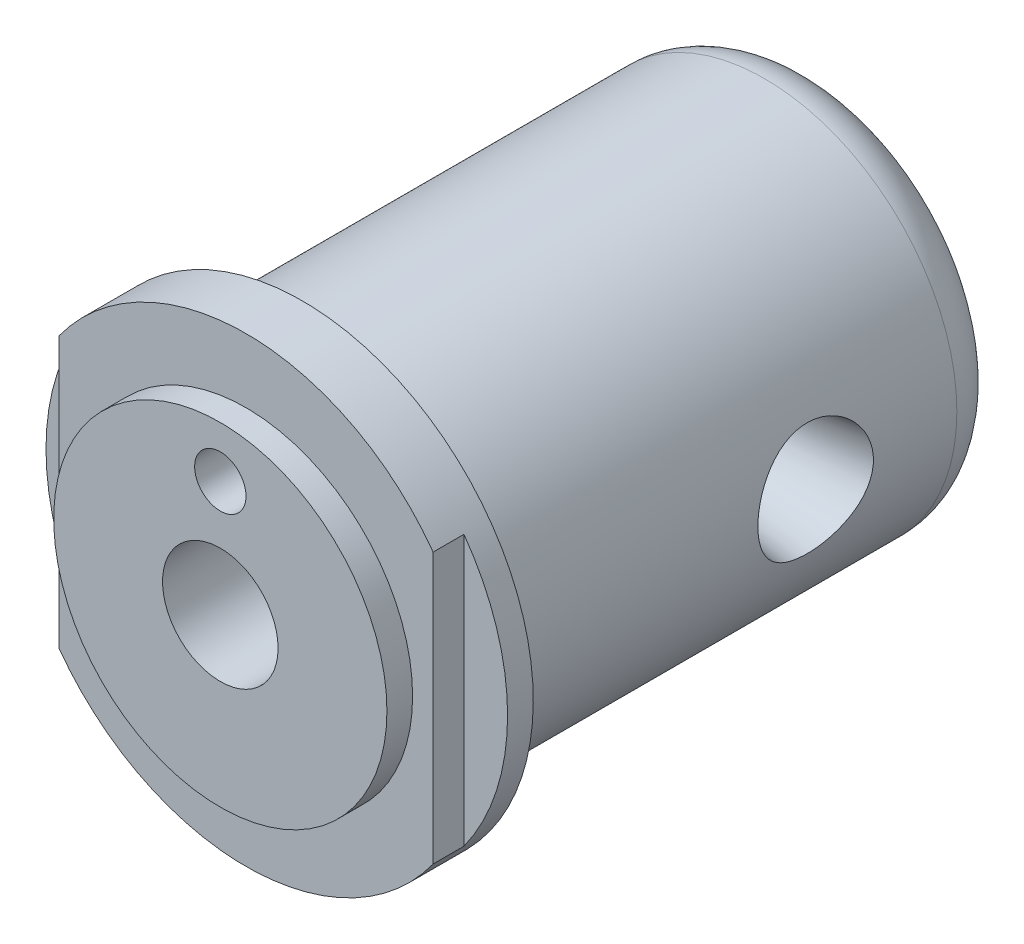
SolidWorks part; units mm, degrees
note: The reader was unsure of these and kept them because the rebuilt part matched: shared geometry of "Sketch1<3>".
material "6061 Alloy"
ref_plane "Front Plane" through (0, 0, 0) normal (0, 0, 1) x (1, 0, 0)
ref_plane "Top Plane" through (0, 0, 0) normal (0, 1, 0) x (1, 0, 0)
ref_plane "Right Plane" through (0, 0, 0) normal (1, 0, 0) x (0, 0, -1)
sketch "Sketch1" plane through (0, 0, 0) normal (0, 0, 1) x (1, 0, 0)
  line L1 (-7.29, -8.99) -> (7.29, -8.99)
  line L2 (-7.29, -8.99) -> (-7.29, 8.99)
  line L3 (-7.29, 8.99) -> (7.29, 8.99)
  line L4 (7.29, -8.99) -> (7.29, 8.99)
  line L5 (-7.29, -8.99) -> (7.29, 8.99) construction
  line L6 (-7.29, 8.99) -> (7.29, -8.99) construction
  circle A0 centre (0, 0) radius 6.49
  circle A1 centre (0, 0) radius 2 construction
  circle A2 centre (0, 4.5) radius 1
  circle A3 centre (0, 0) radius 8.99
  dimension "D1" = 12.98
  dimension "D3" = 2
  dimension "D4" = 4
  dimension "D5" = 17.98
  dimension "D2" = 4.5
  dimension "D6" = 14.58
extrude "Boss-Extrude1" add sketch "Sketch1" along normal blind 1 contours A0 A2 | A2
extrude "Boss-Extrude2" add sketch "Sketch1<3>" against normal blind 1.2 contours L4 A3 L2 A0 | A0 A2 | A2
sketch "Sketch1<3>" plane through (0, 0, 0) normal (0, 0, 1) x (1, 0, 0) same geometry as "Sketch1"
sketch "Sketch2" plane through (0, 0, -1.2) normal (0, 0, -1) x (-1, 0, 0)
  line L4 (-7.29, -8.99) -> (7.29, -8.99)
  line L5 (-7.29, 8.99) -> (-7.29, -8.99)
  line L6 (7.29, 8.99) -> (-7.29, 8.99)
  line L7 (7.29, -8.99) -> (7.29, 8.99)
  line L8 (-7.29, -8.99) -> (7.29, -8.99)
  line L9 (-7.29, 8.99) -> (-7.29, -8.99)
  line L10 (7.29, 8.99) -> (-7.29, 8.99)
  line L11 (7.29, -8.99) -> (7.29, 8.99)
  circle A1 centre (0, 0) radius 8.99
  circle A2 centre (0, 0) radius 8.99
  circle A3 centre (0, 4.5) radius 1
  circle A4 centre (0, 4.5) radius 1
  circle A5 centre (0, 0) radius 6.49
  circle A6 centre (0, 0) radius 6.49
  dimension "D1" = 0
  dimension "D2" = 0
  dimension "D3" = 0
  dimension "D4" = 0
extrude "Boss-Extrude3" add sketch "Sketch2" along normal blind 1
sketch "Sketch3" plane through (0, 0, -2.2) normal (0, 0, -1) x (-1, 0, 0)
  circle A0 centre (0, 0) radius 7.49
  circle A1 centre (0, 0) radius 8.99
  circle A2 centre (0, 0) radius 8.99
  dimension "D2" = 14.98
  dimension "D1" = 0
extrude "Boss-Extrude4" add sketch "Sketch3" along normal blind 20
sketch "Sketch4" plane through (0, 0, -22.2) normal (0, 0, -1) x (-1, 0, 0)
  circle A0 centre (0.1601, 0) radius 5
  circle A1 centre (0, 0) radius 7.49
  circle A2 centre (0, 0) radius 7.49
  dimension "D2" = 14.98
  dimension "D3" = 10
  dimension "D1" = 0
hole_wizard "Ø7.0 (7) Diameter Hole1" positions "Sketch5" profile "Sketch6" hole size "Ø7.0" standard "ISO"
sketch "Sketch5" plane through (0, 0, -22.2) normal (0, 0, -1) x (-1, 0, 0)
  point P0 (0, 0)
sketch "Sketch6" plane through (0, 0, -22.2) normal (1, 0, 0) x (0, 1, 0)
  line L0 (0, 0) -> (0, 16.7)
  line L1 (0, 16.7) -> (3.5, 16.7)
  line L2 (3.5, 16.7) -> (3.5, 0)
  line L5 (3.5, 0) -> (0, 0)
  line L10 (0, 16.7) -> (-3.5, 16.7) construction
  line L11 (0, -6.35) -> (0, 107.95) construction
  dimension "Hole Dia." = 7
  dimension "Hole Depth" = 16.7
  dimension "Drill Angle" = 180
sketch "Sketch7" plane through (0, 0, 1) normal (0, 0, 1) x (1, 0, 0)
  circle A0 centre (0, 4.5) radius 1 construction
  circle A1 centre (0, 4.5) radius 1
  circle A2 centre (0, 0) radius 2 construction
  circle A3 centre (0, 0) radius 2
hole_wizard "Ø2.0mm Dowel Hole1" positions "Sketch8" profile "Sketch9" hole size "Ø2.0" standard "ISO"
sketch "Sketch8" plane through (0, 0, 1) normal (0, 0, 1) x (1, 0, 0)
  point P0 (0, 4.5)
sketch "Sketch9" plane through (0, 4.5, 1) normal (1, 0, 0) x (0, -1, 0)
  line L0 (0, 0) -> (0, 4.6009)
  line L1 (0, 4.6009) -> (1, 4)
  line L2 (1, 4) -> (1, 0)
  line L5 (1, 0) -> (0, 0)
  line L10 (0, 4.6009) -> (-1, 4) construction
  line L11 (0, -6.35) -> (0, 107.95) construction
  dimension "Hole Dia." = 2
  dimension "Hole Depth" = 4
  dimension "Drill Angle" = 118
fillet "Fillet1" radius 2 1 edges at (-7.49, 0, -22.2)
ref_plane "Plane1" through (7.49, 0, 0) normal (1, 0, 0) x (0, 0, -1)
sketch "Sketch10" plane through (7.49, 0, 0) normal (1, 0, 0) x (0, 0, -1)
  line L0 (-1, -6.49) -> (-1, 6.49)
  line L1 (-1, -6.49) -> (-1, 6.49) construction
  line L2 (-1, 6.49) -> (0, 6.49)
  line L3 (-1, 6.49) -> (0, 6.49) construction
  line L4 (0, 6.49) -> (0, 8.99)
  line L5 (0, 6.49) -> (0, 8.99) construction
  line L6 (0, 8.99) -> (2.2, 8.99)
  line L7 (0, 8.99) -> (2.2, 8.99) construction
  line L8 (2.2, 8.99) -> (2.2, 7.49)
  line L9 (2.2, 8.99) -> (2.2, 7.49) construction
  line L10 (2.2, 7.49) -> (20.2, 7.49)
  line L11 (2.2, 7.49) -> (20.2, 7.49) construction
  line L12 (22.2, 5.49) -> (22.2, -5.49)
  line L13 (22.2, 5.49) -> (22.2, -5.49) construction
  line L14 (20.2, -7.49) -> (2.2, -7.49)
  line L15 (20.2, -7.49) -> (2.2, -7.49) construction
  line L16 (2.2, -7.49) -> (2.2, -8.99)
  line L17 (2.2, -7.49) -> (2.2, -8.99) construction
  line L18 (2.2, -8.99) -> (0, -8.99)
  line L19 (2.2, -8.99) -> (0, -8.99) construction
  line L20 (0, -8.99) -> (0, -6.49)
  line L21 (0, -8.99) -> (0, -6.49) construction
  line L22 (0, -6.49) -> (-1, -6.49)
  line L23 (0, -6.49) -> (-1, -6.49) construction
  line L24 (0, 0) -> (22.2, 0) construction
  line L26 (8.95, 2.25) -> (16.95, 2.25)
  line L27 (8.95, 2.25) -> (8.95, -2.25)
  line L28 (8.95, -2.25) -> (16.95, -2.25)
  line L29 (16.95, 2.25) -> (16.95, -2.25)
  arc A0 (22.2, 5.49) -> (20.2, 7.49) centre (20.2, 5.49) ccw
  arc A1 (22.2, 5.49) -> (20.2, 7.49) centre (20.2, 5.49) ccw construction
  arc A2 (20.2, -7.49) -> (22.2, -5.49) centre (20.2, -5.49) ccw
  arc A3 (20.2, -7.49) -> (22.2, -5.49) centre (20.2, -5.49) ccw construction
  circle A4 centre (14.7, 0) radius 2.25
  dimension "D2" = 4.5
  dimension "D1" = 12.5
  dimension "D3" = 8
hole_wizard "Ø4.5 (4.5) Diameter Hole1" [suppressed] positions "Sketch12" profile "Sketch13" hole size "Ø4.5" standard "ISO"
sketch "Sketch12" plane through (7.49, 0, 0) normal (1, 0, 0) x (0, 0, -1)
  point P0 (14.7, 0)
sketch "Sketch13" plane through (7.49, 0, -14.7) normal (0, 1, 0) x (0, 0, -1)
  line L0 (0, 0) -> (0, 1.5)
  line L1 (0, 1.5) -> (2.25, 1.3624)
  line L2 (2.25, 1.3624) -> (2.25, 0)
  line L5 (2.25, 0) -> (0, 0)
  line L10 (0, 1.5) -> (-2.25, 1.3624) construction
  line L11 (0, -6.35) -> (0, 107.95) construction
  dimension "Hole Dia." = 4.5
  dimension "Hole Depth" = 1.5
  dimension "Drill Angle" = 173
hole_wizard "Ø4.5 (4.5) Diameter Hole2" positions "Sketch14" profile "Sketch15" hole size "Ø4.5" standard "ISO" end condition through all
sketch "Sketch14" plane through (0, 0, 1) normal (0, 0, 1) x (1, 0, 0)
  point P0 (0, 0)
sketch "Sketch15" plane through (0, 0, 1) normal (1, 0, 0) x (0, -1, 0)
  line L0 (0, 0) -> (0, 23.2)
  line L1 (0, 23.2) -> (2.25, 23.2)
  line L2 (2.25, 23.2) -> (2.25, 0)
  line L5 (2.25, 0) -> (0, 0)
  line L11 (0, -6.35) -> (0, 107.95) construction
  dimension "Thru Hole Dia." = 4.5
  dimension "Thru Hole Depth" = 23.2
sketch "Sketch16" [suppressed] plane through (0, 0, 0) normal (0, 1, 0) x (1, 0, 0)
  line L0 (-5.49, 22.2) -> (5.49, 22.2)
  line L1 (-5.49, 22.2) -> (5.49, 22.2)
  line L2 (7.49, 20.2) -> (7.49, 2.2)
  line L3 (7.49, 20.2) -> (7.49, 2.2)
  line L4 (7.49, 2.2) -> (8.99, 2.2)
  line L5 (7.49, 2.2) -> (8.99, 2.2)
  line L6 (8.99, 2.2) -> (8.99, 1.2)
  line L7 (8.99, 2.2) -> (8.99, 1.2)
  line L8 (8.99, 1.2) -> (7.29, 1.2)
  line L9 (8.99, 1.2) -> (7.29, 1.2)
  line L10 (7.29, 1.2) -> (7.29, 0)
  line L11 (7.29, 1.2) -> (7.29, 0)
  line L12 (7.29, 0) -> (6.49, 0)
  line L13 (7.29, 0) -> (6.49, 0)
  line L14 (6.49, 0) -> (6.49, -1)
  line L15 (6.49, 0) -> (6.49, -1)
  line L16 (6.49, -1) -> (-6.49, -1)
  line L17 (6.49, -1) -> (-6.49, -1)
  line L18 (-6.49, -1) -> (-6.49, 0)
  line L19 (-6.49, -1) -> (-6.49, 0)
  line L20 (-6.49, 0) -> (-7.29, 0)
  line L21 (-6.49, 0) -> (-7.29, 0)
  line L22 (-7.29, 0) -> (-7.29, 1.2)
  line L23 (-7.29, 0) -> (-7.29, 1.2)
  line L24 (-7.29, 1.2) -> (-8.99, 1.2)
  line L25 (-7.29, 1.2) -> (-8.99, 1.2)
  line L26 (-8.99, 1.2) -> (-8.99, 2.2)
  line L27 (-8.99, 1.2) -> (-8.99, 2.2)
  line L28 (-8.99, 2.2) -> (-7.49, 2.2)
  line L29 (-8.99, 2.2) -> (-7.49, 2.2)
  line L30 (-7.49, 2.2) -> (-7.49, 20.2)
  line L31 (-7.49, 2.2) -> (-7.49, 20.2)
  line L32 (7.49, 16.932) -> (6.49, 13.2)
  line L33 (6.49, 13.2) -> (6.49, 11.2)
  line L34 (6.49, 11.2) -> (7.49, 10.2)
  line L35 (0, 22.2) -> (0, -1.2024) construction
  arc A0 (7.49, 20.2) -> (5.49, 22.2) centre (5.49, 20.2) ccw
  arc A1 (7.49, 20.2) -> (5.49, 22.2) centre (5.49, 20.2) ccw
  arc A2 (-5.49, 22.2) -> (-7.49, 20.2) centre (-5.49, 20.2) ccw
  arc A3 (-5.49, 22.2) -> (-7.49, 20.2) centre (-5.49, 20.2) ccw
  dimension "D1" = 15
  dimension "D2" = 3.732
  dimension "D3" = 2
  dimension "D4" = 45
  dimension "D5" = 14.732
  dimension "D6" = 8
sketch "Sketch17" [suppressed] plane through (7.49, 0, 0) normal (1, 0, 0) x (0, 0, -1)
  line L1 (10.2, 1.7013) -> (16.932, 1.7013)
  line L2 (10.2, 1.7013) -> (10.2, -2.7987)
  line L3 (10.2, -2.7987) -> (16.932, -2.7987)
  line L4 (16.932, 1.7013) -> (16.932, -2.7987)
  point P0 (16.932, 0)
  point P2 (10.2, 0)
  dimension "D1" = 4.5
extrude "Cut-Extrude1" [suppressed] cut sketch "Sketch17" against normal offset from surface (0.2369 mm away) 4.2
revolve "Cut-Revolve1" [suppressed] cut sketch "Sketch16" about L35
extrude "Cut-Extrude2" cut sketch "Sketch10" against normal up to surface draft 7 contours A4 L27 up to face at (-3.5, 0, -5.5)
